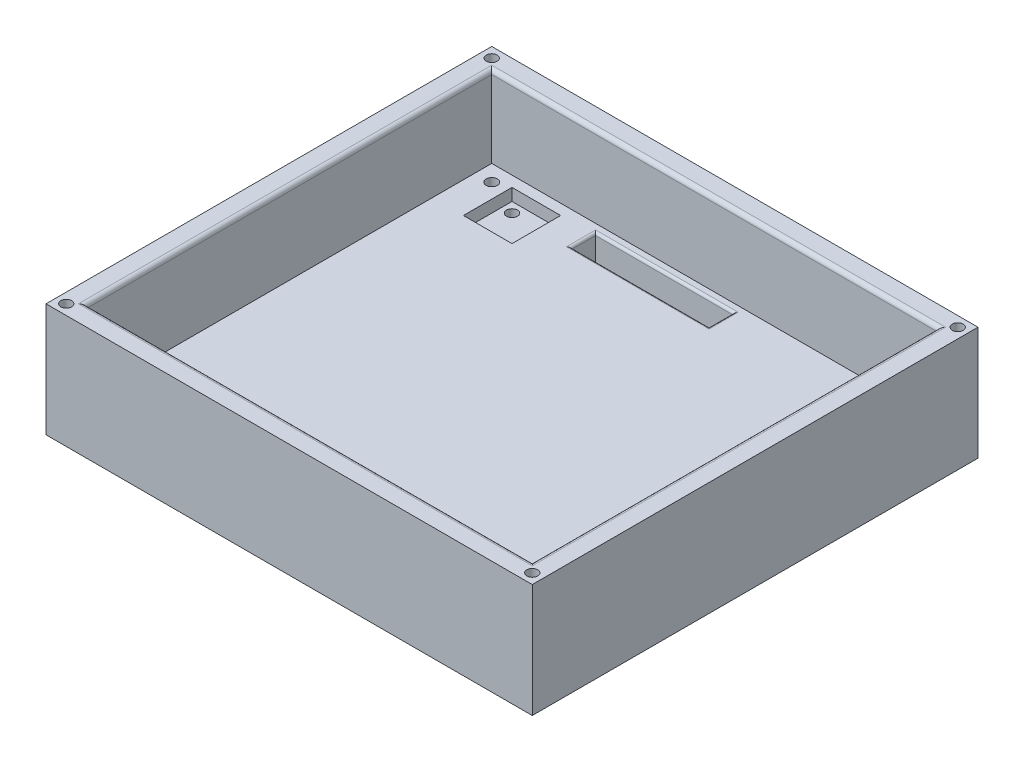
SolidWorks part; units mm, degrees
ref_plane "Front Plane" through (0, 0, 0) normal (0, 0, 1) x (1, 0, 0)
ref_plane "Top Plane" through (0, 0, 0) normal (0, 1, 0) x (1, 0, 0)
ref_plane "Right Plane" through (0, 0, 0) normal (1, 0, 0) x (0, 0, -1)
sketch "Sketch1" plane through (0, 0, 0) normal (0, 1, 0) x (1, 0, 0)
  line L1 (-49.9999, -49.9999) -> (49.9999, -49.9999) construction
  line L2 (-49.9999, -49.9999) -> (-49.9999, 49.9999) construction
  line L3 (-49.9999, 49.9999) -> (49.9999, 49.9999) construction
  line L4 (49.9999, -49.9999) -> (49.9999, 49.9999) construction
  line L5 (-49.9999, -49.9999) -> (49.9999, 49.9999) construction
  line L6 (-49.9999, 49.9999) -> (49.9999, -49.9999) construction
  line L7 (-76.2, -69.85) -> (76.2, -69.85)
  line L8 (-76.2, -69.85) -> (-76.2, 69.85)
  line L9 (-76.2, 69.85) -> (76.2, 69.85)
  line L10 (76.2, -69.85) -> (76.2, 69.85)
  line L11 (-76.2, -69.85) -> (76.2, 69.85) construction
  line L12 (-76.2, 69.85) -> (76.2, -69.85) construction
  line L13 (-49.9999, 49.9999) -> (-44.9199, 49.9999) construction
  line L14 (-49.9999, 49.9999) -> (-49.9999, 44.9199) construction
  line L15 (-49.9999, 44.9199) -> (-44.9199, 44.9199) construction
  line L16 (-44.9199, 49.9999) -> (-44.9199, 44.9199) construction
  line L17 (-44.9199, 44.9199) -> (-60.1599, 44.9199)
  line L18 (-44.9199, 44.9199) -> (-44.9199, 60.1599)
  line L19 (-44.9199, 60.1599) -> (-60.1599, 60.1599)
  line L20 (-60.1599, 44.9199) -> (-60.1599, 60.1599)
  line L21 (49.9999, -49.9999) -> (43.6499, -49.9999) construction
  line L22 (49.9999, -49.9999) -> (49.9999, -43.6499) construction
  line L23 (49.9999, -43.6499) -> (43.6499, -43.6499) construction
  line L24 (43.6499, -49.9999) -> (43.6499, -43.6499) construction
  line L25 (43.6499, -43.6499) -> (58.8899, -43.6499)
  line L26 (43.6499, -43.6499) -> (43.6499, -58.8899)
  line L27 (43.6499, -58.8899) -> (58.8899, -58.8899)
  line L28 (58.8899, -43.6499) -> (58.8899, -58.8899)
  point P0 (0, 0)
  point P6 (0, 0)
  dimension "D1" = 99.9998
  dimension "D2" = 99.9998
  dimension "D3" = 139.7
  dimension "D4" = 152.4
  dimension "D5" = 5.08
  dimension "D6" = 5.08
  dimension "D7" = 15.24
  dimension "D8" = 15.24
  dimension "D9" = 6.35
  dimension "D10" = 6.35
  dimension "D11" = 15.24
  dimension "D12" = 15.24
extrude "Boss-Extrude1" add sketch "Sketch1" against normal blind 10.16
extrude "Boss-Extrude2" add sketch "Sketch1<2>" along normal blind 6.35 from surface contours L20 L17 L18 L19 | L28 L25 L26 L27 region at (-52.5399, 0, -52.5399) region at (51.2699, 0, 51.2699) starting at face at (51.2699, -10.16, 51.2699)
sketch "Sketch1<2>" plane through (0, 0, 0) normal (0, 1, 0) x (1, 0, 0) same geometry as "Sketch1"
sketch "Sketch3" plane through (0, 0, 0) normal (0, 1, 0) x (1, 0, 0)
  line L0 (76.2, -69.85) -> (76.2, 69.85) construction
  line L2 (-76.2, 69.85) -> (-76.2, -69.85)
  line L3 (-69.85, 63.5) -> (69.85, 63.5)
  line L4 (76.2, 69.85) -> (76.2, -69.85)
  line L6 (-76.2, 69.85) -> (76.2, 69.85)
  line L7 (-76.2, 69.85) -> (-76.2, -69.85)
  line L8 (-76.2, -69.85) -> (76.2, -69.85)
  line L9 (-69.85, 63.5) -> (-69.85, -63.5)
  line L10 (76.2, 69.85) -> (-76.2, 69.85) construction
  line L11 (-76.2, -69.85) -> (76.2, -69.85)
  line L12 (-76.2, -69.85) -> (-76.2, 69.85)
  line L13 (-69.85, -63.5) -> (69.85, -63.5)
  line L14 (76.2, -69.85) -> (76.2, 69.85)
  line L15 (76.2, 69.85) -> (-76.2, 69.85)
  line L16 (76.2, 69.85) -> (76.2, -69.85)
  line L18 (69.85, 63.5) -> (69.85, -63.5)
  line L19 (-76.2, -69.85) -> (76.2, -69.85) construction
  line M22 (76.2, -69.85) -> (76.2, 69.85)
  line M23 (76.2, 69.85) -> (-76.2, 69.85)
  line M24 (-76.2, 69.85) -> (-76.2, -69.85)
  line M25 (-76.2, -69.85) -> (76.2, -69.85)
  dimension "D1" = 6.35
  dimension "D2" = 6.35
  dimension "D3" = 6.35
  dimension "D4" = 6.35
extrude "Boss-Extrude3" add sketch "Sketch3" along normal blind 25.4 contours L3 L18 L13 L9 M25 M22 M23 M24 region at (0, 0, -67.7826)
sketch "Sketch4" plane through (0, 25.4, 0) normal (0, 1, 0) x (1, 0, 0)
  line L0 (-76.2, -69.85) -> (76.2, -69.85) construction
  line L1 (-76.2, 69.85) -> (-76.2, -69.85) construction
  line L2 (76.2, -69.85) -> (76.2, 69.85) construction
  line L3 (76.2, 69.85) -> (-76.2, 69.85) construction
  circle A0 centre (-73.025, -66.675) radius 1.7018
  circle A1 centre (73.025, -66.675) radius 1.7018
  circle A2 centre (73.025, 66.675) radius 1.7018
  circle A3 centre (-73.025, 66.675) radius 1.7018
  dimension "D1" = 3.4036
  dimension "D4" = 3.4036
  dimension "D5" = 3.4036
  dimension "D6" = 3.4036
  dimension "D2" = 3.175
  dimension "D3" = 3.175
  dimension "D7" = 3.175
  dimension "D8" = 3.175
  dimension "D9" = 3.175
  dimension "D10" = 3.175
  dimension "D11" = 3.175
  dimension "D12" = 3.175
extrude "Cut-Extrude1" cut sketch "Sketch4" against normal blind 17.78
sketch "Sketch5" plane through (0, 0, 0) normal (0, 1, 0) x (1, 0, 0)
  line L1 (-34.7599, 53.34) -> (8.4201, 53.34)
  line L2 (-34.7599, 53.34) -> (-34.7599, 60.96)
  line L3 (-34.7599, 60.96) -> (8.4201, 60.96)
  line L4 (8.4201, 53.34) -> (8.4201, 60.96)
  line L5 (-44.9199, 60.1599) -> (-44.9199, 44.9199) construction
  line L6 (-69.85, 63.5) -> (69.85, 63.5) construction
  dimension "D1" = 10.16
  dimension "D2" = 7.62
  dimension "D3" = 43.18
  dimension "D4" = 2.54
extrude "Cut-Extrude2" cut sketch "Sketch5" against normal through all
fillet "Fillet1" radius 0.762 4 edges at (8.4201, 0, -57.15) (-13.1699, 0, -53.34) (-34.7599, 0, -57.15) (-13.1699, 0, -60.96)
fillet "Fillet2" radius 1.27 4 edges at (0, 25.4, 63.5) (-69.85, 25.4, 0) (69.85, 25.4, 0) (0, 25.4, -63.5)
sketch "Sketch6" plane through (0, -3.81, 0) normal (0, 1, 0) x (1, 0, 0)
  line L0 (-60.1599, 60.1599) -> (-60.1599, 44.9199) construction
  line L1 (-44.9199, 60.1599) -> (-60.1599, 60.1599) construction
  line L2 (43.6499, -58.8899) -> (58.8899, -58.8899) construction
  line L4 (58.8899, -58.8899) -> (58.8899, -43.6499) construction
  circle A0 centre (-56.9849, 56.9849) radius 1.7018
  circle A1 centre (55.7149, -55.7149) radius 1.7018
  dimension "D1" = 3.4036
  dimension "D4" = 3.4036
  dimension "D2" = 3.175
  dimension "D3" = 3.175
  dimension "D5" = 3.175
  dimension "D6" = 3.175
extrude "Cut-Extrude3" cut sketch "Sketch6" against normal blind 3.81 contours A1 | A0 region at (-56.9849, -3.81, -56.9849) region at (55.7149, -3.81, 55.7149)
sketch "Sketch7" plane through (0, 0, 0) normal (0, 1, 0) x (1, 0, 0)
  line L0 (-69.85, 63.5) -> (-69.85, -63.5) construction
  line L1 (-69.85, 63.5) -> (69.85, 63.5) construction
  line L2 (-69.85, -63.5) -> (69.85, -63.5) construction
  line L3 (-69.85, -63.5) -> (69.85, -63.5) construction
  line L4 (69.85, 63.5) -> (69.85, -63.5) construction
  circle A0 centre (-64.77, 58.42) radius 1.7653
  circle A1 centre (-64.77, -58.42) radius 1.7653
  circle A2 centre (64.77, -58.42) radius 1.7653
  circle A3 centre (64.77, 58.42) radius 1.7653
  dimension "D1" = 3.5306
  dimension "D2" = 3.5306
  dimension "D3" = 3.5306
  dimension "D4" = 3.5306
  dimension "D5" = 5.08
  dimension "D6" = 5.08
  dimension "D7" = 5.08
  dimension "D8" = 5.08
  dimension "D9" = 5.08
  dimension "D10" = 5.08
  dimension "D11" = 5.08
  dimension "D12" = 5.08
extrude "Cut-Extrude4" cut sketch "Sketch7" against normal through all contours A0 | A3 | A2 | A1 region at (-64.77, 0, -58.42) region at (-64.77, 0, 58.42) region at (64.77, 0, 58.42) region at (64.77, 0, -58.42)
